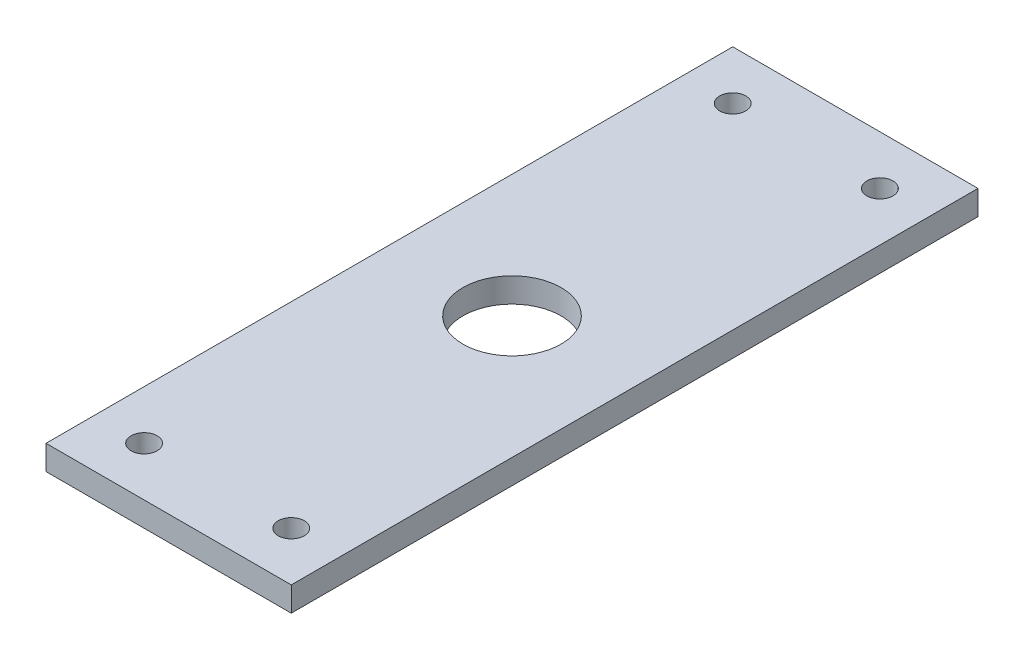
SolidWorks part; units mm, degrees
material "Galvanized Steel"
ref_plane "Front Plane" through (0, 0, 0) normal (0, 0, 1) x (1, 0, 0)
ref_plane "Top Plane" through (0, 0, 0) normal (0, 1, 0) x (1, 0, 0)
ref_plane "Right Plane" through (0, 0, 0) normal (1, 0, 0) x (0, 0, -1)
sketch "Sketch1" plane through (0, 0, 0) normal (0, 1, 0) x (1, 0, 0)
  line L1 (-31.75, 88.9) -> (31.75, 88.9)
  line L2 (-31.75, 88.9) -> (-31.75, -88.9)
  line L3 (-31.75, -88.9) -> (31.75, -88.9)
  line L4 (31.75, 88.9) -> (31.75, -88.9)
  line L5 (-19.05, -76.2) -> (19.05, -76.2) construction
  line L6 (-19.05, -76.2) -> (-19.05, 76.2) construction
  line L7 (-19.05, 76.2) -> (19.05, 76.2) construction
  line L8 (19.05, -76.2) -> (19.05, 76.2) construction
  line L9 (-19.05, -76.2) -> (19.05, 76.2) construction
  line L10 (-19.05, 76.2) -> (19.05, -76.2) construction
  circle A0 centre (0, 0) radius 12.7
  circle A1 centre (19.05, 76.2) radius 3.3782
  circle A2 centre (-19.05, 76.2) radius 3.3782
  circle A3 centre (-19.05, -76.2) radius 3.3782
  circle A4 centre (19.05, -76.2) radius 3.3782
  point P0 (0, 0)
  point P8 (0, 88.9)
  point P9 (31.75, 0)
  point P10 (0, 0)
  dimension "D2" = 25.4
  dimension "D4" = 6.7564
  dimension "D1" = 177.8
  dimension "D3" = 63.5
  dimension "D5" = 38.1
  dimension "D6" = 152.4
extrude "Boss-Extrude1" add sketch "Sketch1" along normal blind 6.35
